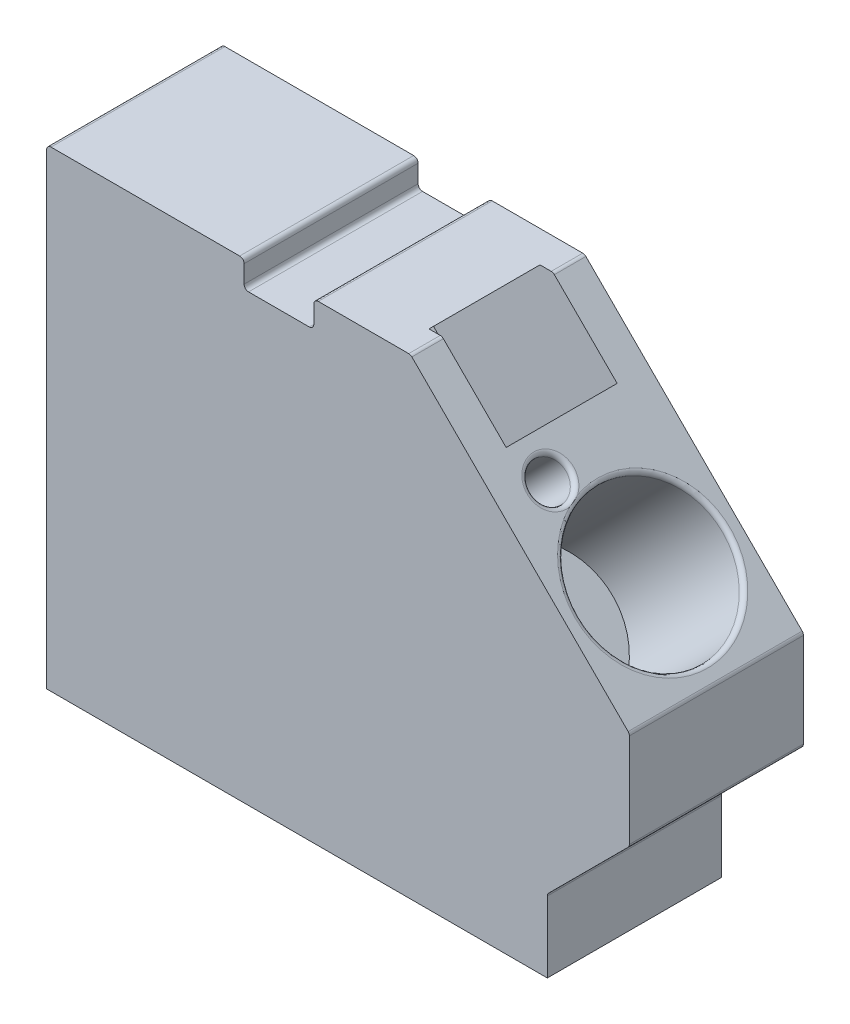
SolidWorks part; units mm, degrees
ref_plane "Front Plane" through (0, 0, 0) normal (0, 0, 1) x (1, 0, 0)
ref_plane "Top Plane" through (0, 0, 0) normal (0, 1, 0) x (1, 0, 0)
ref_plane "Right Plane" through (0, 0, 0) normal (1, 0, 0) x (0, 0, -1)
sketch "Sketch1" plane through (0, 0, 0) normal (0, 0, 1) x (1, 0, 0)
  line L0 (0, 0) -> (0, 26.7208)
  line L1 (0.254, 26.9748) -> (11.049, 26.9748)
  line L2 (20.9024, 26.9004) -> (33.2758, 14.527)
  line L3 (33.3502, 14.3474) -> (33.3502, 8.9698)
  line L4 (33.2758, 8.7902) -> (28.7276, 4.242)
  line L5 (28.6532, 4.0624) -> (28.6532, 0)
  line L6 (28.6532, 0) -> (0, 0)
  line L7 (15.5448, 26.9748) -> (20.7228, 26.9748)
  line L9 (11.303, 26.7208) -> (11.303, 25.7048)
  line L10 (11.557, 25.4508) -> (15.0368, 25.4508)
  line L11 (15.2908, 26.7208) -> (15.2908, 25.7048)
  arc A0 (28.7276, 4.242) -> (28.6532, 4.0624) centre (28.9072, 4.0624) ccw
  arc A1 (33.3502, 8.9698) -> (33.2758, 8.7902) centre (33.0962, 8.9698) cw
  arc A2 (33.2758, 14.527) -> (33.3502, 14.3474) centre (33.0962, 14.3474) cw
  arc A3 (20.7228, 26.9748) -> (20.9024, 26.9004) centre (20.7228, 26.7208) cw
  arc A4 (0, 26.7208) -> (0.254, 26.9748) centre (0.254, 26.7208) cw
  arc A5 (11.303, 25.7048) -> (11.557, 25.4508) centre (11.557, 25.7048) ccw
  arc A6 (15.0368, 25.4508) -> (15.2908, 25.7048) centre (15.0368, 25.7048) ccw
  arc A7 (15.5448, 26.9748) -> (15.2908, 26.7208) centre (15.5448, 26.7208) ccw
  arc A8 (11.049, 26.9748) -> (11.303, 26.7208) centre (11.049, 26.7208) cw
  point P12 (33.3502, 8.8646)
  point P15 (33.3502, 14.4526)
  point P18 (20.828, 26.9748)
  point P21 (0, 26.9748)
  point P28 (11.303, 25.4508)
  point P31 (15.2908, 25.4508)
  dimension "D7" = 0.254
  dimension "D11" = 0.254
  dimension "D1" = 33.3502
  dimension "D2" = 20.828
  dimension "D3" = 45
  dimension "D4" = 45
  dimension "D5" = 5.588
  dimension "D6" = 26.9748
  dimension "D8" = 11.303
  dimension "D9" = 3.9878
  dimension "D10" = 1.524
extrude "Extrude1" add sketch "Sketch1" along normal blind 9.9568
sketch "Sketch2" plane through (23.9014, 23.9014, 0) normal (0.7071, 0.7071, 0) x (0, 0, -1)
  line L0 (-4.9784, 16.5322) -> (-4.9784, 10.1267) construction
  line L1 (-8.1534, 4.8762) -> (-1.8034, 4.8762)
  line L2 (-8.1534, 4.8762) -> (-8.1534, -0.8388)
  line L3 (-8.1534, -0.8388) -> (-1.8034, -0.8388)
  line L4 (-1.8034, 4.8762) -> (-1.8034, -0.8388)
  line L5 (-4.9784, 4.2412) -> (-4.9784, -27.516) construction
  line L6 (-9.9568, 4.2412) -> (0, 4.2412) construction
  circle A0 centre (-4.9784, -8.2048) radius 4.191
  circle A1 centre (-7.0739, -2.8878) radius 1.0795
  dimension "D1" = 8.382
  dimension "D6" = 2.159
  dimension "D2" = 6.35
  dimension "D3" = 3.175
  dimension "D4" = 7.366
  dimension "D5" = 5.715
  dimension "D7" = 5.715
  dimension "D8" = 0.635
extrude "Extrude2" cut sketch "Sketch2" against normal blind 9.144
fillet "Fillet1" radius 0.254 2 edges at (26.7396, 21.0632, 4.9784) (25.1801, 22.6227, 7.0739)
